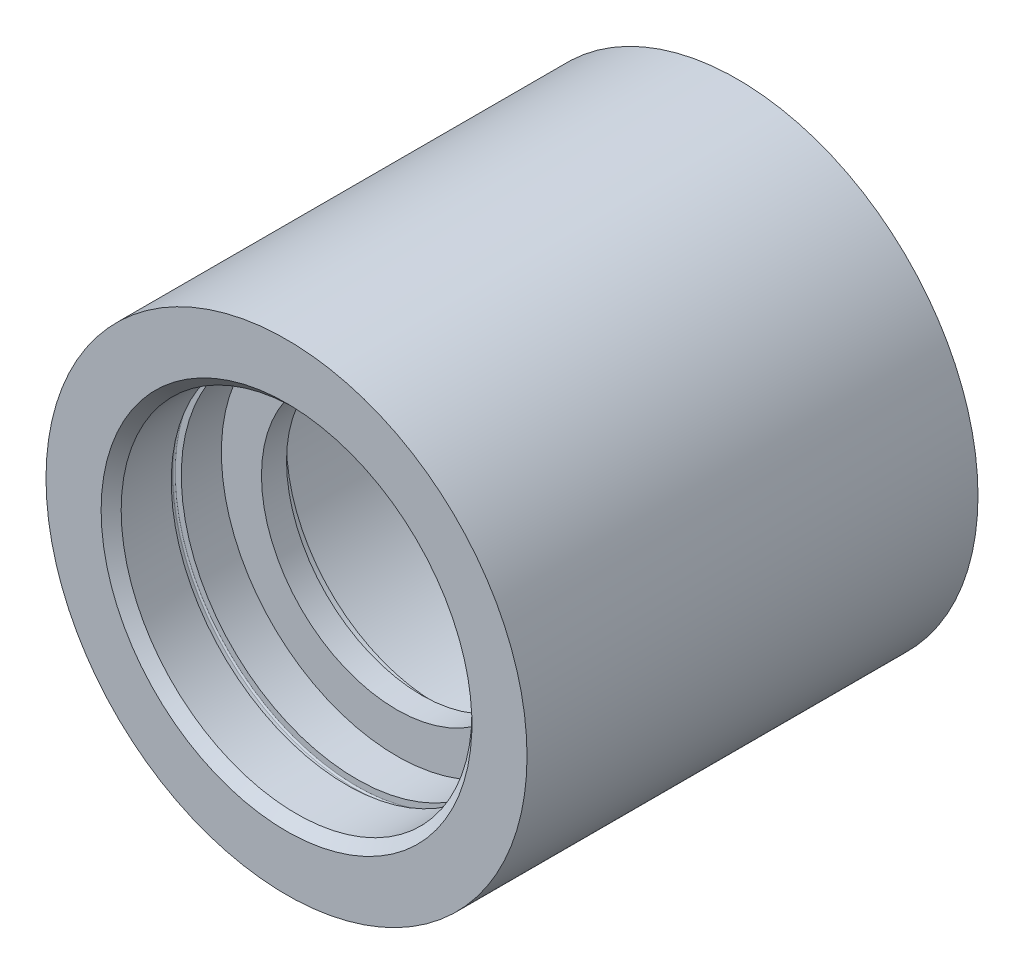
SolidWorks part; units mm, degrees
material "AISI 304"
ref_plane "Спереди" through (0, 0, 0) normal (0, 0, 1) x (1, 0, 0)
ref_plane "Сверху" through (0, 0, 0) normal (0, 1, 0) x (1, 0, 0)
ref_plane "Справа" through (0, 0, 0) normal (1, 0, 0) x (0, 0, -1)
sketch "Эскиз1" plane through (0, 0, 0) normal (1, 0, 0) x (0, 0, -1)
  line L0 (0, 0) -> (0, 48) construction
  line L1 (0, 48) -> (90, 48)
  line L2 (90, 48) -> (90, 40)
  line L3 (90, 40) -> (30, 40)
  line L6 (22, 27) -> (22, 35)
  line L7 (22, 35) -> (0, 35)
  line L8 (0, 35) -> (0, 48)
  line L9 (0, 0) -> (110.0063, 0) construction
  line L10 (22, 27) -> (27, 27)
  line L11 (27, 27) -> (27, 30)
  line L12 (27, 30) -> (30, 30)
  line L13 (30, 30) -> (30, 40)
  dimension "D1" = 48
  dimension "D2" = 35
  dimension "D3" = 27
  dimension "D4" = 40
  dimension "D5" = 22
  dimension "D6" = 8
  dimension "D7" = 8
  dimension "63" = 60
  dimension "D8" = 30
  dimension "D9" = 3
  dimension "D10" = 5
revolve "Повернуть1" add sketch "Эскиз1" angle 360 about L9
ref_plane "Плоскость1" through (0, 0, -14) normal (0, 0, 1) x (1, 0, 0)
sketch "Эскиз2" plane through (0, 0, -14) normal (0, 0, 1) x (1, 0, 0)
  circle A0 centre (0, 0) radius 36.5
  dimension "D1" = 73
extrude "Вырез-Вытянуть1" cut sketch "Эскиз2" along normal blind 2
ref_plane "Плоскость2" through (0, 0, -69) normal (0, 0, -1) x (-1, 0, 0)
sketch "Эскиз3" plane through (0, 0, -69) normal (0, 0, -1) x (-1, 0, 0)
  circle A0 centre (0, 0) radius 41.75
  dimension "D1" = 83.5
extrude "Вырез-Вытянуть2" cut sketch "Эскиз3" along normal blind 2.3
fillet "Скругление1" radius 0.3 4 edges at (-41.75, 0, -71.3) (-41.75, 0, -69) (36.5, 0, -12) (36.5, 0, -14)
chamfer "Фаска2" distance 2 angle 45 2 edges at (35, 0, 0) (40, 0, -90)
ref_axis "Ось1" through (0, 0, -80.9) along (0, 0, 1)
ref_plane "Плоскость3" through (0, 0, 0) normal (0.9239, 0.3827, 0) x (0, 0, 1)
